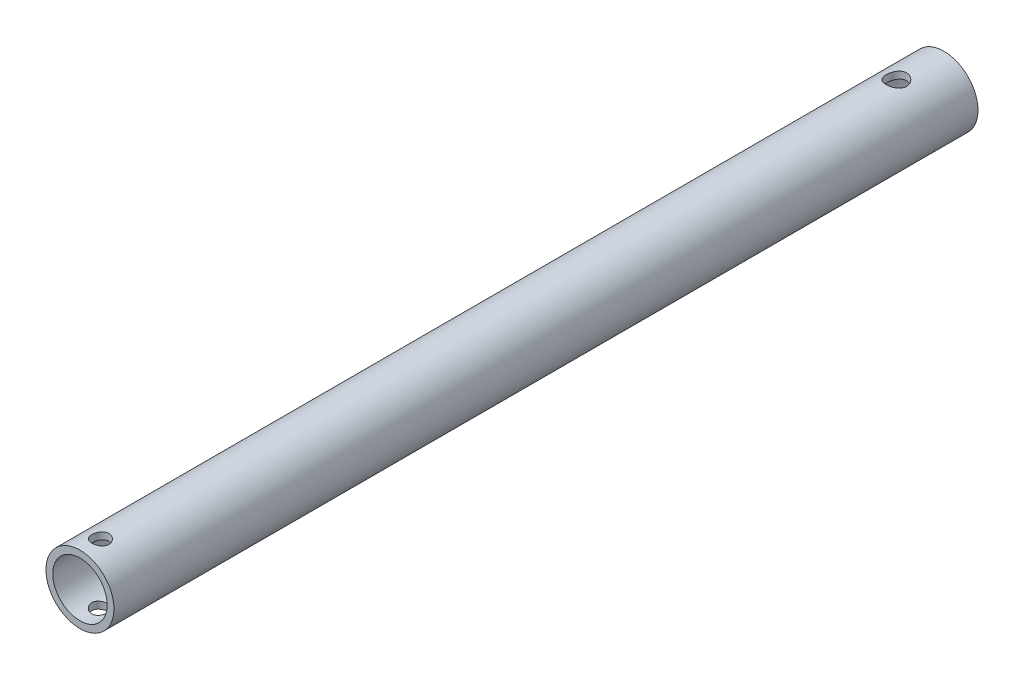
SolidWorks part; units mm, degrees
ref_plane "Front Plane" through (0, 0, 0) normal (0, 0, 1) x (1, 0, 0)
ref_plane "Top Plane" through (0, 0, 0) normal (0, 1, 0) x (1, 0, 0)
ref_plane "Right Plane" through (0, 0, 0) normal (1, 0, 0) x (0, 0, -1)
sketch "Sketch1" plane through (0, 0, 0) normal (0, 0, 1) x (1, 0, 0)
  line L0 (-15.875, 0) -> (15.875, 0) construction
  line L1 (0, -15.875) -> (0, 15.875) construction
  circle A0 centre (0, 0) radius 15.875
  circle A1 centre (0, 0) radius 12.7
  point P4 (0, 0)
  point P9 (0, 0)
  point P10 (12.7, 0)
  dimension "ID" = 25.4
  dimension "OD" = 31.75
  dimension "Wall Thickness" = 3.175
sketch "Sketch2" plane through (0, 0, 0) normal (1, 0, 0) x (0, 0, -1)
  line L0 (457.2, 15.875) -> (-457.2, 15.875) construction
  line L1 (0, 15.875) -> (0, -15.875) construction
  point P3 (-381, 15.875)
  point P4 (0, 15.875)
  point P5 (381, 15.875)
  dimension "D2" = 76.2
  dimension "Length" = 914.4
sketch "Sketch3" plane through (0, 0, 0) normal (0, 0, 1) x (1, 0, 0)
  line L0 (0, -15.875) -> (0, 15.875) construction
  circle A0 centre (0, 0) radius 15.875
  circle A1 centre (0, 0) radius 12.7
  circle A2 centre (0, 0) radius 12.7 construction
extrude "Boss-Extrude1" add sketch "Sketch3" along normal mid plane 914.4
sketch "Sketch4" plane through (0, 0, 457.2) normal (0, 0, 1) x (1, 0, 0)
  circle A0 centre (0, 0) radius 24.6875
extrude "Cut-Extrude1" cut sketch "Sketch4" against normal offset from surface (511.175 mm away) 403.225 up to face at (15.875, 0, -457.2)
sketch "Sketch5" plane through (0, 0, 0) normal (0, 1, 0) x (1, 0, 0)
  line L0 (-15.875, 53.975) -> (15.875, 53.975) construction
  line L1 (0, 63.5) -> (-15.875, 63.5) construction
  line L2 (-15.875, 457.2) -> (-15.875, 53.975) construction
  line L3 (0, 63.5) -> (15.875, 63.5) construction
  line L4 (15.875, 53.975) -> (15.875, 457.2) construction
  circle A0 centre (0, 63.5) radius 3.9687
  circle A1 centre (0, 434.975) radius 4.7625
  dimension "D1" = 7.9375
  dimension "D3" = 9.525
  dimension "D2" = 9.525
  dimension "D4" = 381
extrude "Cut-Extrude2" cut sketch "Sketch5" against normal through all both and the other way through all
equation "\"D1@Boss-Extrude1\" = \"Length@Sketch2\""
equation "\"D2@Sketch2\"=\"D1@Sketch2\""
